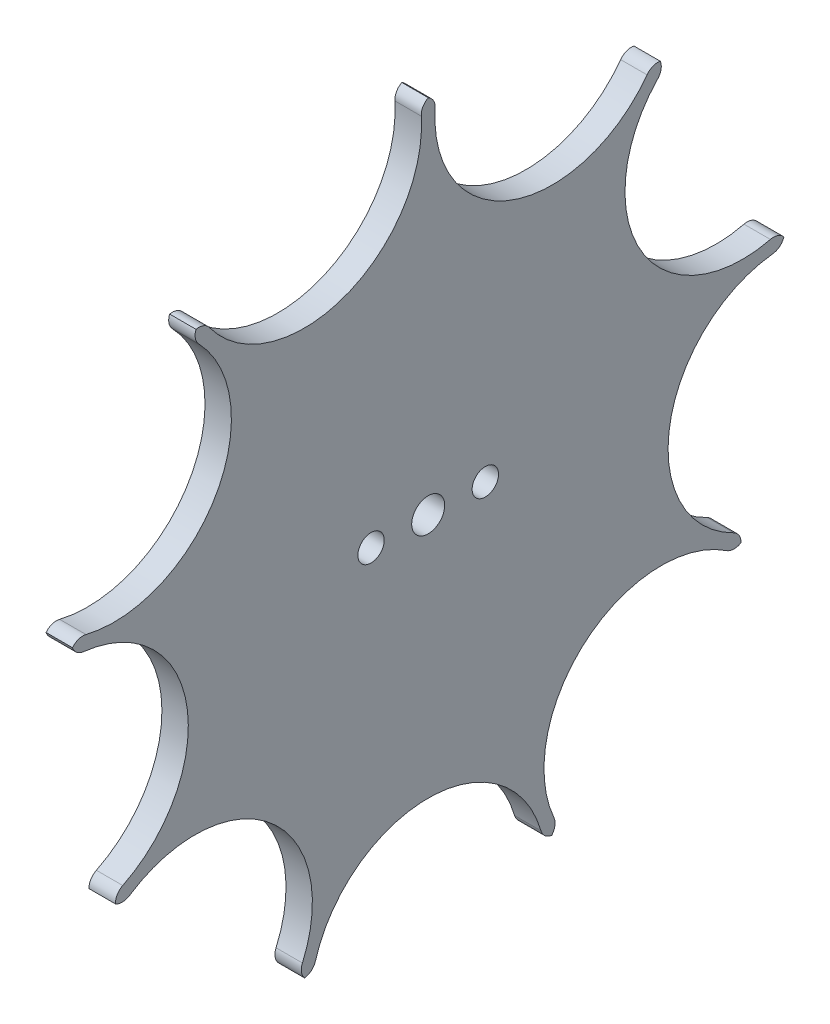
SolidWorks part; units mm, degrees
ref_plane "Front Plane" through (0, 0, 0) normal (0, 0, 1) x (1, 0, 0)
ref_plane "Top Plane" through (0, 0, 0) normal (0, 1, 0) x (1, 0, 0)
ref_plane "Right Plane" through (0, 0, 0) normal (1, 0, 0) x (0, 0, -1)
sketch "Sketch1" plane through (0, 0, 0) normal (1, 0, 0) x (0, 0, -1)
  circle A0 centre (0, 0) radius 34.925
  dimension "D1" = 69.85
extrude "Boss-Extrude1" add sketch "Sketch1" along normal mid plane 2.54
sketch "Sketch3" plane through (0, 0, 0) normal (1, 0, 0) x (0, 0, -1)
  line L0 (0, 0) -> (0, -50000) construction
  line L1 (0, 0) -> (0, -34.925) construction
  circle A0 centre (0, -34.925) radius 11.303
  circle A1 centre (0, 0) radius 34.925 construction
  dimension "D1" = 22.606
  dimension "D2" = 180
extrude "Cut-Extrude1" cut sketch "Sketch3" against normal mid plane 12.7
pattern_circular "CirPattern1" count 9 over 360 about axis through (1.27, 0, 0) along (1, 0, 0) of "Cut-Extrude1"
fillet "Fillet1" radius 1.27 18 edges at (0, -16.7316, -30.6563) (0, 5.2375, -34.53) (0, 6.8883, -34.239) (0, 26.2077, -23.0849) (0, 27.2851, -21.8009) (0, 34.9149, -0.8381) (0, 34.9149, 0.8381) (0, 27.2851, 21.8009) (0, 26.2077, 23.0849) (0, 6.8883, 34.239) (0, 5.2375, 34.53) (0, -16.7316, 30.6563) (0, -18.1833, 29.8182) (0, -32.5227, 12.7292) (0, -33.096, 11.154) (0, -33.096, -11.154) (0, -32.5227, -12.7292) (0, -18.1833, -29.8182)
sketch "radii geometry" plane through (0, 0, 0) normal (1, 0, 0) x (0, 0, -1)
  circle A0 centre (0, 0) radius 23.622 construction
  arc A1 (0.6668, 33.5657) -> (21.0649, 26.1414) centre (11.9451, 32.8188) ccw construction
  circle A2 centre (0, 0) radius 34.925 construction
sketch "Sketch5" plane through (0, 0, 0) normal (1, 0, 0) x (0, 0, -1)
  circle A0 centre (0, 0) radius 1.5875
  dimension "D1" = 3.175
extrude "Cut-Extrude2" cut sketch "Sketch5" against normal mid plane 12.7
ref_axis "Rotating_axis" through (-1.7463, 0, 0) along (1, 0, 0)
sketch "Sketch6" plane through (1.27, 0, 0) normal (1, 0, 0) x (0, 0, -1)
  circle A0 centre (-5.5, 0) radius 1.27
  circle A1 centre (5.5, 0) radius 1.27
  point P4 (0, 0)
  point P6 (4.6933, 0)
  dimension "D1" = 2.54
  dimension "D2" = 5.5
  dimension "D3" = 11
extrude "Cut-Extrude3" cut sketch "Sketch6" against normal through all
